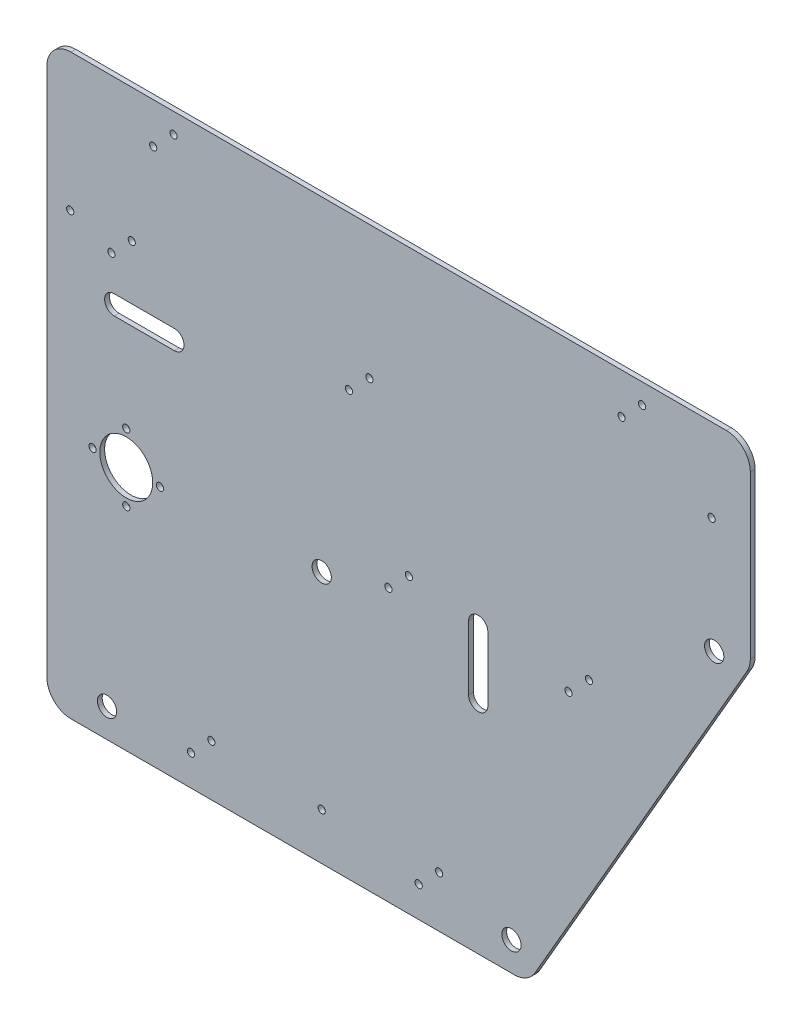
SolidWorks part; units mm, degrees
ref_plane "Front Plane" through (0, 0, 0) normal (0, 0, 1) x (1, 0, 0)
ref_plane "Top Plane" through (0, 0, 0) normal (0, 1, 0) x (1, 0, 0)
ref_plane "Right Plane" through (0, 0, 0) normal (1, 0, 0) x (0, 0, -1)
sketch "Sketch1" plane through (0, 0, 0) normal (0, 0, 1) x (1, 0, 0)
  line L0 (100, 80) -> (192.376, 80)
  line L1 (-100, -80) -> (100, -80)
  line L2 (-100, -80) -> (-100, 80)
  line L3 (-100, 80) -> (100, 80)
  line L4 (100, -80) -> (100, 80)
  line L5 (-100, -80) -> (100, 80) construction
  line L6 (-100, 80) -> (100, -80) construction
  line L7 (192.376, 80) -> (100, -80)
  line L8 (100, 80) -> (100, -80)
  line L10 (-100, 80) -> (192.376, 80)
  line L11 (-100, 80) -> (-100, 110)
  line L12 (-100, 110) -> (192.376, 110)
  line L13 (192.376, 80) -> (192.376, 110)
  point P0 (0, 0)
  dimension "D1" = 160
  dimension "D2" = 200
  dimension "D3" = 30
  dimension "D4" = 30
extrude "Boss-Extrude1" add sketch "Sketch1" along normal blind 2 contours L1 L4 L3 L2 | L7 L0 L4 | L11 L10 L13 L12 region at (0, 0, 0) region at (130.792, 26.6667, 0)
sketch "Sketch2" plane through (0, 0, 2) normal (0, 0, 1) x (1, 0, 0)
  line L0 (-100, -80) -> (100, -80) construction
  line L1 (192.376, 80) -> (100, -80) construction
  line L2 (79.2904, 11.2418) -> (79.2904, 37.9086) construction
  line L3 (-100, -80) -> (-100, 110) construction
  line L4 (-72, 78) -> (-47, 78) construction
  line L7 (-100, 110) -> (192.376, 110) construction
  line L8 (75.2904, 11.2418) -> (75.2904, 37.9086)
  line L9 (-72, 82) -> (-47, 82)
  line L10 (-72, 74) -> (-47, 74)
  line L11 (-100, -80) -> (-100, 110) construction
  line L12 (83.2904, 11.2418) -> (83.2904, 37.9086)
  circle A0 centre (93.0718, -68) radius 4
  circle A1 centre (177.3649, 78) radius 4
  circle A2 centre (-67, 22) radius 11
  circle A3 centre (-75, -68) radius 4
  circle A4 centre (-53, 22) radius 1.5
  circle A5 centre (-67, 36) radius 1.5
  circle A6 centre (-81, 22) radius 1.5
  circle A7 centre (-67, 8) radius 1.5
  circle A11 centre (54.5495, -67.2426) radius 1.5
  circle A12 centre (63.0348, -58.7574) radius 1.5
  circle A13 centre (14.2259, -60.5) radius 1.5
  circle A14 centre (-40.1271, -67.2426) radius 1.5
  circle A15 centre (-31.6419, -58.7574) radius 1.5
  circle A16 centre (-90.2956, 102.8814) radius 1.5
  circle A17 centre (-73.1863, 96.1388) radius 1.5
  circle A18 centre (-64.701, 104.6241) radius 1.5
  circle A19 centre (25.5556, 96.1388) radius 1.5
  circle A20 centre (34.0408, 104.6241) radius 1.5
  circle A21 centre (41.9695, 33.1388) radius 1.5
  circle A22 centre (50.4548, 41.6241) radius 1.5
  circle A23 centre (-39.813, 33.1388) radius 1.5 construction
  circle A24 centre (-31.3277, 41.6241) radius 1.5 construction
  circle A25 centre (116.8113, 33.1388) radius 1.5
  circle A26 centre (125.2966, 41.6241) radius 1.5
  circle A27 centre (79.2904, 25) radius 4 construction
  circle A28 centre (14.2259, 25) radius 4
  arc A29 (-72, 82) -> (-72, 74) centre (-72, 78) ccw
  arc A30 (-47, 74) -> (-47, 82) centre (-47, 78) ccw
  circle A31 centre (176.3056, 125.4889) radius 1.5
  arc A32 (75.2904, 11.2418) -> (83.2904, 11.2418) centre (79.2904, 11.2418) ccw
  arc A33 (83.2904, 37.9086) -> (75.2904, 37.9086) centre (79.2904, 37.9086) ccw
  circle A34 centre (-55.8147, 143.1388) radius 1.5
  circle A35 centre (-47.3294, 151.6241) radius 1.5
  circle A36 centre (138.8916, 143.1388) radius 1.5
  circle A37 centre (147.3769, 151.6241) radius 1.5
  point P26 (-59.5, 78)
  point P87 (79.2904, 24.5752)
  dimension "D3" = 8
  dimension "D4" = 8
  dimension "D9" = 22
  dimension "D10" = 8
  dimension "D12" = 3
  dimension "D13" = 3
  dimension "D14" = 3
  dimension "D15" = 3
  dimension "D16" = 14
  dimension "D20" = 8
  dimension "D22" = 4
  dimension "D25" = 3
  dimension "D26" = 3
  dimension "D29" = 8
  dimension "D28" = 3
  dimension "D1" = 12
  dimension "D2" = 12
  dimension "D5" = 32
  dimension "D6" = 12
  dimension "D7" = 88
  dimension "D8" = 33
  dimension "D11" = 12
  dimension "D17" = 14
  dimension "D18" = 14
  dimension "D19" = 14
  dimension "D21" = 85
  dimension "D23" = 28
  dimension "D24" = 25
  dimension "D27" = 25
  dimension "D30" = 8
extrude "Cut-Extrude1" cut sketch "Sketch2" against normal blind 3
sketch "Sketch4" plane through (0, 0, 2) normal (0, 0, 1) x (1, 0, 0)
  line L0 (192.376, 80) -> (192.376, 110) construction
  line L1 (-100, 110) -> (192.376, 110)
  line L2 (-100, 110) -> (-100, 160)
  line L3 (-100, 160) -> (192.376, 160)
  line L4 (192.376, 110) -> (192.376, 160)
  dimension "D1" = 50
extrude "Boss-Extrude2" add sketch "Sketch4" against normal blind 2
fillet "Fillet1" radius 10 5 edges at (192.376, 160, 1) (192.376, 80, 1) (100, -80, 1) (-100, -80, 1) (-100, 160, 1)
sketch "Sketch5" plane through (0, 0, 2) normal (0, 0, 1) x (1, 0, 0)
  circle A2 centre (-55.8147, 143.1388) radius 1.5
  circle A3 centre (-47.3294, 151.6241) radius 1.5
  circle A4 centre (138.8916, 143.1388) radius 1.5
  circle A5 centre (147.3769, 151.6241) radius 1.5
  circle A6 centre (176.3056, 125.4889) radius 1.5
  dimension "D1" = 3
extrude "Cut-Extrude2" cut sketch "Sketch5" against normal blind 11
